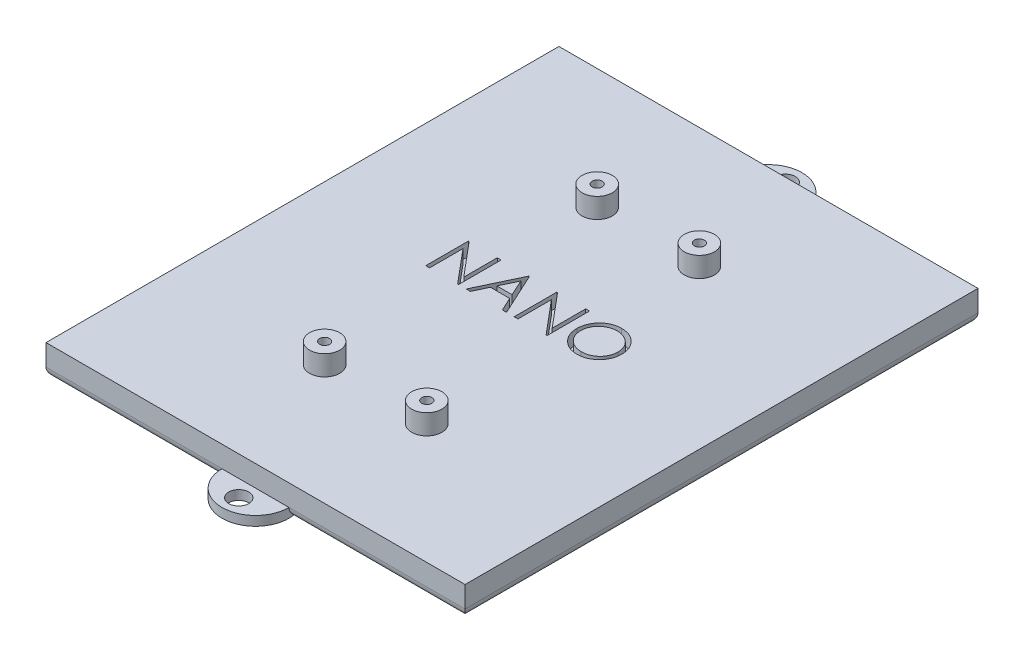
SolidWorks part; units mm, degrees
ref_plane "Front Plane" through (0, 0, 0) normal (0, 0, 1) x (1, 0, 0)
ref_plane "Top Plane" through (0, 0, 0) normal (0, 1, 0) x (1, 0, 0)
ref_plane "Right Plane" through (0, 0, 0) normal (1, 0, 0) x (0, 0, -1)
sketch "Sketch1" plane through (0, 0, 0) normal (0, 1, 0) x (1, 0, 0)
  line L0 (-31.25, 38.25) -> (31.25, 38.25)
  line L5 (-31.25, 38.25) -> (-31.25, -38.25)
  line L6 (-31.25, -38.25) -> (31.25, -38.25)
  line L7 (31.25, 38.25) -> (31.25, -38.25)
  point P11 (-31.25, 0)
  point P12 (0, -38.25)
  dimension "D3" = 76.5
  dimension "D4" = 62.5
extrude "Boss-Extrude1" add sketch "Sketch1" along normal blind 4.575
sketch "Sketch4" plane through (0, 0, 0) normal (0, 1, 0) x (1, 0, 0)
  line L0 (-5, -38.25) -> (5, -38.25)
  line L2 (-31.25, -38.25) -> (31.25, -38.25) construction
  line L4 (0, -38.25) -> (0, -43.25) construction
  arc A0 (-5, -38.25) -> (5, -38.25) centre (0, -38.25) ccw
  circle A2 centre (0, -40.75) radius 1.5
  dimension "D2" = 3
  dimension "D3" = 5
extrude "Boss-Extrude3" add sketch "Sketch4" along normal blind 1.4
mirror "Mirror1" about plane through (0, 0, 0) normal (0, 0, 1) of "Boss-Extrude3"
fillet "Fillet1" radius 1.4 6 edges at (-18.125, 0, 38.25) (18.125, 0, 38.25) (31.25, 0, 0) (18.125, 0, -38.25) (-18.125, 0, -38.25) (-31.25, 0, 0)
sketch "Sketch2" plane through (0, 4.575, 0) normal (0, 1, 0) x (1, 0, 0)
  line L1 (-7.6205, 20.3255) -> (7.6205, 20.3255) construction
  line L2 (7.6205, 20.3255) -> (7.6205, -20.3255) construction
  line L3 (7.6205, -20.3255) -> (-7.6205, -20.3255) construction
  line L4 (-7.6205, -20.3255) -> (-7.6205, 20.3255) construction
  circle A8 centre (-7.6205, 20.3255) radius 0.75
  circle A9 centre (7.6205, 20.3255) radius 0.75
  circle A10 centre (-7.6205, -20.3255) radius 0.75
  circle A11 centre (7.6205, -20.3255) radius 0.75
  circle A12 centre (-7.6205, -20.3255) radius 2.25
  circle A13 centre (7.6205, -20.3255) radius 2.25
  circle A14 centre (7.6205, 20.3255) radius 2.25
  circle A15 centre (-7.6205, 20.3255) radius 2.25
  point P8 (7.6205, 0)
  point P9 (0, 20.3255)
  dimension "D1" = 1.5
  dimension "D4" = 1.5
  dimension "D2" = 40.651
  dimension "D3" = 15.241
extrude "Boss-Extrude2" add sketch "Sketch2" along normal blind 3
sketch "Sketch3" plane through (0, 4.575, 0) normal (0, 1, 0) x (1, 0, 0)
  circle A0 centre (7.6205, -20.3255) radius 0.75
  circle A1 centre (-7.6205, -20.3255) radius 0.75
  circle A2 centre (-7.6205, 20.3255) radius 0.75
  circle A3 centre (7.6205, 20.3255) radius 0.75
  circle A6 centre (-7.6205, -20.3255) radius 0.75 construction
  point P12 (0, 0)
  point P13 (-5.3705, -24.3431)
  point P14 (-7.6205, -20.3255)
  point P16 (0, 0)
  point P17 (0, 0)
  point P18 (0, 0)
  point P21 (7.6205, -20.3255)
  point P23 (14.0733, 19.5755)
  point P24 (7.6205, 20.3255)
  point P26 (-7.6205, 20.3255)
extrude "Cut-Extrude1" cut sketch "Sketch3" against normal offset from surface (3.575 mm away) 1 up to face at (0, 0, 0)
sketch "Sketch5" plane through (0, 4.575, 0) normal (0, 1, 0) x (1, 0, 0)
  line L0 (-15, 0) -> (15, 0) construction
  text T0 "NANO\r\n" font "Century Gothic" height in points 24
  point P4 (14.3725, 0)
  point P5 (10.1548, 0)
  point P6 (0, 0)
  point P7 (0, 0)
  dimension "D1" = 30
extrude "Letters" cut sketch "Sketch5" against normal blind 2
